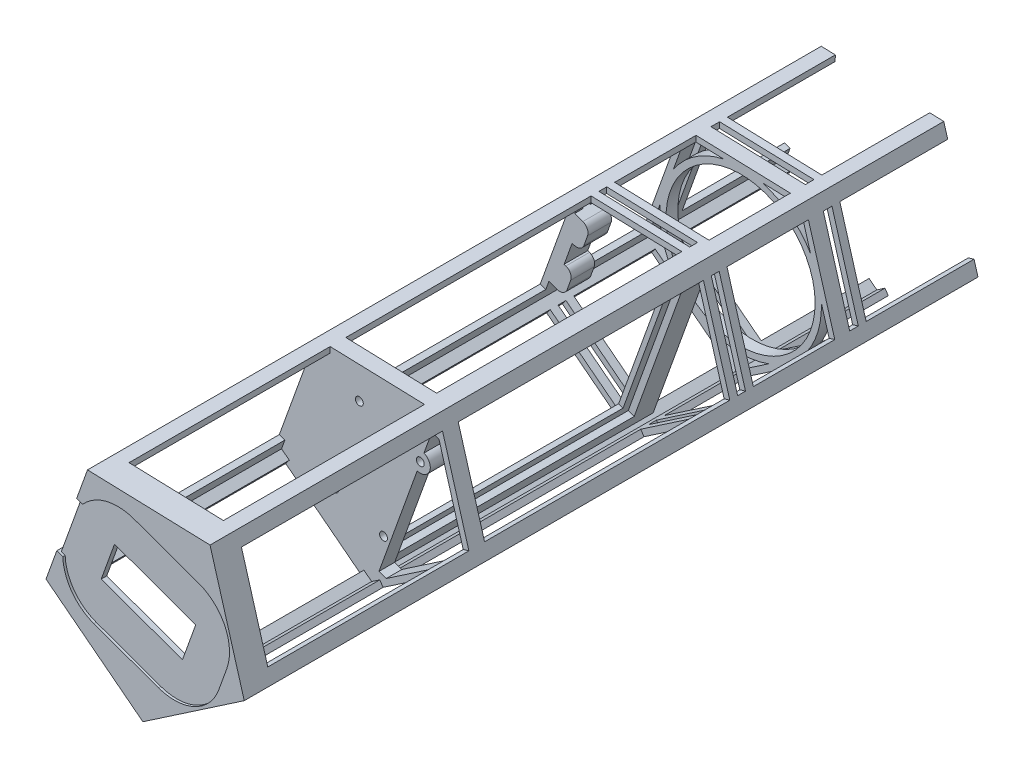
SolidWorks part; units mm, degrees
ref_plane "Front Plane" through (0, 0, 0) normal (0, 0, 1) x (1, 0, 0)
ref_plane "Top Plane" through (0, 0, 0) normal (0, 1, 0) x (1, 0, 0)
ref_plane "Right Plane" through (0, 0, 0) normal (1, 0, 0) x (0, 0, -1)
sketch "Sketch3" plane through (0, 0, 0) normal (0, 0, 1) x (1, 0, 0)
  line L0 (0, 0) -> (16.2851, 21.0012) construction
  line L1 (15.1489, 19.536) -> (-13.8986, 20.4445)
  line L2 (-13.8986, 20.4445) -> (-23.7387, -6.9006)
  line L3 (-23.7387, -6.9006) -> (-0.7728, -24.7093)
  line L4 (-0.7728, -24.7093) -> (23.2611, -8.3705)
  line L5 (0, 0) -> (29.9163, 0) construction
  line L6 (0, 0) -> (25.0057, -8.9983) construction
  line L10 (-0.8307, -26.5625) -> (25.0057, -8.9983)
  line L11 (25.0057, -8.9983) -> (16.2851, 21.0012)
  line L12 (16.2851, 21.0012) -> (-14.941, 21.9778)
  line L13 (-14.941, 21.9778) -> (-25.5191, -7.4182)
  line L14 (-25.5191, -7.4182) -> (-0.8307, -26.5625)
  line L15 (23.2611, -8.3705) -> (15.1489, 19.536)
  circle A0 centre (0, 0) radius 20 construction
  point P4 (0, 0)
  point P14 (0, 0)
  dimension "D2" = 40
extrude "Boss-Extrude2" add sketch "Sketch3" along normal blind 185
ref_plane "Plane1" through (0, 0, 92.5) normal (0, 0, 1) x (1, 0, 0)
sketch "Sketch4" plane through (0, 0, 0) normal (0, 0, -1) x (-1, 0, 0)
  line L0 (14.745, 18.0921) -> (16.1564, 18.6)
  line L1 (13.8986, 20.4445) -> (23.7387, -6.9006) construction
  line L2 (14.941, 21.9778) -> (25.5191, -7.4182) construction
  line L3 (24.3036, -4.0404) -> (22.8922, -4.5483)
  line L4 (22.8922, -4.5483) -> (14.745, 18.0921)
  line L5 (24.3036, -4.0404) -> (16.1564, 18.6)
  dimension "D1" = 2.5
  dimension "D2" = 2.5
extrude "Cut-Extrude1" cut sketch "Sketch4" against normal offset from surface (180 mm away) 5 up to face at (0, 0, 185)
ref_point "Point1"
ref_axis "Axis1" through (0, 0, 185) along (0, 0, 1)
pattern_circular "CirPattern1" count 5 over 360 about axis through (0, 0, 185) along (0, 0, 1) of "Cut-Extrude1"
ref_plane "Plane2" through (0, 0, 92.5) normal (0, 0, 1) x (1, 0, 0)
sketch "Sketch5" plane through (0, 0, 92.5) normal (0, 0, 1) x (1, 0, 0)
  line L0 (-2.0696, -25.6018) -> (14.7182, 21.0502) construction
  line L2 (-24.1133, -8.5083) -> (-1.8275, -25.7895) construction
  line L3 (23.2611, -8.3705) -> (0, 0) construction
  line L4 (-4.3961, -23.7977) -> (11.7756, 21.1422)
  line L8 (-2.0696, -25.6018) -> (-4.3961, -23.7977)
  line L10 (14.7182, 21.0502) -> (11.7756, 21.1422)
  line L11 (-2.0696, -25.6018) -> (14.7182, 21.0502)
  line L12 (-22.8004, 22.2236) -> (6.2471, 21.3151) construction
  dimension "D1" = 18
  dimension "D2" = 2.8
extrude "Boss-Extrude3" add sketch "Sketch5" along normal mid plane 64.5
sketch "Sketch6" plane through (0, 0, 124.75) normal (0, 0, 1) x (1, 0, 0)
  line L5 (-25.5191, -7.4182) -> (-0.8307, -26.5625)
  line L6 (-0.8307, -26.5625) -> (25.0057, -8.9983)
  line L7 (25.0057, -8.9983) -> (16.2851, 21.0012)
  line L8 (16.2851, 21.0012) -> (-14.941, 21.9778)
  line L9 (-14.941, 21.9778) -> (-25.5191, -7.4182)
  line L10 (-25.5191, -7.4182) -> (-0.8307, -26.5625)
  line L11 (-0.8307, -26.5625) -> (25.0057, -8.9983)
  line L12 (25.0057, -8.9983) -> (16.2851, 21.0012)
  line L13 (16.2851, 21.0012) -> (-14.941, 21.9778)
  line L14 (-14.941, 21.9778) -> (-25.5191, -7.4182)
  dimension "D1" = 0
extrude "Boss-Extrude4" add sketch "Sketch6" along normal blind 4
sketch "Sketch7" plane through (0, 0, 124.75) normal (0, 0, -1) x (-1, 0, 0)
  line L0 (-3.6897, -1.3278) -> (20.23, 7.2798) construction
  line L1 (-11.7756, 21.1422) -> (4.3961, -23.7977) construction
  line L2 (16.1564, 18.6) -> (24.3036, -4.0404) construction
  line L4 (19.0326, -2.4504) -> (13.1071, 14.0159)
  line L5 (0.2139, -9.2223) -> (-5.7115, 7.244)
  line L7 (19.0326, -2.4504) -> (-5.7115, 7.244) construction
  line L8 (0.2139, -9.2223) -> (13.1071, 14.0159) construction
  line L9 (9.6232, -5.8364) -> (3.6978, 10.63) construction
  line L11 (-11.7756, 21.1422) -> (4.3961, -23.7977) construction
  arc A0 (-5.7115, 7.244) -> (13.1071, 14.0159) centre (3.6978, 10.63) cw
  arc A1 (0.2139, -9.2223) -> (19.0326, -2.4504) centre (9.6232, -5.8364) ccw
  point P7 (6.6605, 2.3968)
  point P9 (13.0092, -15.2457)
  point P14 (0.3119, 20.0393)
  point P15 (0, 0)
  point P16 (7.1485, 2.5724)
  point P17 (7.4662, 2.6867)
  dimension "D1" = 37.5
  dimension "D2" = 20
  dimension "D3" = 1
extrude "Cut-Extrude2" cut sketch "Sketch7" against normal blind 2
sketch "Sketch8" plane through (6.3243, -2.2758, 0) normal (0.9409, -0.3386, 0) x (0, 0, -1)
  line L0 (-60.25, 0) -> (-124.75, 0) construction
  line L1 (-124.75, -23.2131) -> (-124.75, 23.2131) construction
  line L3 (-60.25, -23.2131) -> (-60.25, 23.2131) construction
  line L5 (-123, -20.5) -> (-123, 20.5)
  line L6 (-123, -20.5) -> (-62, -20.5)
  line L7 (-123, 20.5) -> (-62, 20.5)
  line L8 (-62, -20.5) -> (-62, 20.5)
  line L14 (-62, 20.5) -> (-123, -20.5) construction
  line L15 (-62, -20.5) -> (-123, 20.5) construction
  point P2 (0, 0)
  point P5 (0, 0)
  point P6 (0, 0)
  point P11 (-92.5, 0)
  point P14 (-92.5, 0)
  dimension "D1" = 61
  dimension "D2" = 41
extrude "Cut-Extrude3" cut sketch "Sketch8" against normal blind 1.6
sketch "Sketch9" plane through (4.8189, -1.7341, 0) normal (0.9409, -0.3386, 0) x (0, 0, -1)
  line L8 (-121, -18.5) -> (-64, -18.5)
  line L9 (-64, -18.5) -> (-64, 18.5)
  line L10 (-64, 18.5) -> (-121, 18.5)
  line L11 (-121, 18.5) -> (-121, -18.5)
  line L12 (-121, -18.5) -> (-64, -18.5)
  line L13 (-64, -18.5) -> (-64, 18.5)
  line L14 (-64, 18.5) -> (-121, 18.5)
  line L15 (-121, 18.5) -> (-121, -18.5)
  dimension "D1" = 2
extrude "Cut-Extrude4" cut sketch "Sketch9" against normal up to surface (1.2 mm away) up to face at (3.6897, -1.3278, 92.5)
sketch "Sketch10" plane through (0, 0, 60.25) normal (0, 0, -1) x (-1, 0, 0)
  line L25 (-23.2611, -8.3705) -> (0.7728, -24.7093)
  line L26 (0.7728, -24.7093) -> (23.7387, -6.9006)
  line L27 (23.7387, -6.9006) -> (13.8986, 20.4445)
  line L28 (13.8986, 20.4445) -> (-15.1489, 19.536)
  line L29 (-15.1489, 19.536) -> (-23.2611, -8.3705)
  line L30 (0.8307, -26.5625) -> (25.5191, -7.4182)
  line L31 (-25.0057, -8.9983) -> (0.8307, -26.5625)
  line L32 (-16.2851, 21.0012) -> (-25.0057, -8.9983)
  line L33 (14.941, 21.9778) -> (-16.2851, 21.0012)
  line L34 (25.5191, -7.4182) -> (14.941, 21.9778)
  line L40 (0.8307, -26.5625) -> (25.5191, -7.4182)
  line L41 (-25.0057, -8.9983) -> (0.8307, -26.5625)
  line L42 (-16.2851, 21.0012) -> (-25.0057, -8.9983)
  line L43 (14.941, 21.9778) -> (-16.2851, 21.0012)
  line L44 (25.5191, -7.4182) -> (14.941, 21.9778)
  point P8 (0, 0)
  point P11 (-0.8687, -22.1155)
  dimension "D1" = 0
extrude "Boss-Extrude5" add sketch "Sketch10" against normal blind 2
sketch "Sketch11" plane through (0, 0, 60.25) normal (0, 0, -1) x (-1, 0, 0)
  line L0 (3.8621, -22.3137) -> (4.3961, -23.7977)
  line L1 (4.3961, -23.7977) -> (3.6676, -24.3627)
  line L2 (-11.2416, 19.6582) -> (-11.7756, 21.1422)
  line L3 (-11.7756, 21.1422) -> (-12.697, 21.1134)
  line L4 (21.7631, -8.4326) -> (3.8621, -22.3137)
  line L7 (3.8621, -22.3137) -> (-11.2416, 19.6582)
  line L9 (-14.1842, 19.5662) -> (1.5355, -24.1178)
  line L10 (-14.1842, 19.5662) -> (1.5355, -24.1178)
  line L11 (-12.697, 21.1134) -> (11.3529, 21.8656) construction
  line L13 (3.8621, -22.3137) -> (-11.2416, 19.6582) construction
  line L18 (22.6823, -9.618) -> (3.6676, -24.3627) construction
  line L19 (3.8621, -22.3137) -> (-11.2416, 19.6582)
  line L27 (-11.2416, 19.6582) -> (11.3998, 20.3663)
  line L31 (1.5355, -24.1178) -> (2.7484, -23.1773)
  line L33 (1.5355, -24.1178) -> (2.7484, -23.1773)
  line L35 (2.7484, -23.1773) -> (3.6676, -24.3627)
  line L37 (2.7484, -23.1773) -> (3.6676, -24.3627)
  line L39 (3.6676, -24.3627) -> (22.6823, -9.618)
  line L41 (22.6823, -9.618) -> (21.7631, -8.4326)
  line L43 (11.3998, 20.3663) -> (11.3529, 21.8656)
  line L45 (11.3529, 21.8656) -> (-12.697, 21.1134)
  line L47 (-12.697, 21.1134) -> (-12.6502, 19.6141)
  line L48 (-12.697, 21.1134) -> (-12.6502, 19.6141)
  line L49 (-12.6502, 19.6141) -> (-14.1842, 19.5662)
  line L50 (-12.6502, 19.6141) -> (-14.1842, 19.5662)
  dimension "D1" = 0
extrude "Boss-Extrude6" add sketch "Sketch11" along normal blind 4
sketch "Sketch12" plane through (0, 0, 56.25) normal (0, 0, -1) x (-1, 0, 0)
  line L0 (0.7728, -24.7093) -> (23.7387, -6.9006)
  line L1 (23.7387, -6.9006) -> (13.8986, 20.4445)
  line L2 (13.8986, 20.4445) -> (-15.1489, 19.536)
  line L3 (-15.1489, 19.536) -> (-23.2611, -8.3705)
  line L4 (-23.2611, -8.3705) -> (0.7728, -24.7093)
  line L5 (0.8307, -26.5625) -> (25.5191, -7.4182)
  line L6 (-25.0057, -8.9983) -> (0.8307, -26.5625)
  line L7 (-16.2851, 21.0012) -> (-25.0057, -8.9983)
  line L8 (14.941, 21.9778) -> (-16.2851, 21.0012)
  line L9 (25.5191, -7.4182) -> (14.941, 21.9778)
  line L10 (0.8307, -26.5625) -> (25.5191, -7.4182)
  line L11 (-25.0057, -8.9983) -> (0.8307, -26.5625)
  line L12 (-16.2851, 21.0012) -> (-25.0057, -8.9983)
  line L13 (14.941, 21.9778) -> (-16.2851, 21.0012)
  line L14 (25.5191, -7.4182) -> (14.941, 21.9778)
  point P15 (0, -21.7043)
  dimension "D1" = 0
extrude "Boss-Extrude7" add sketch "Sketch12" against normal blind 2
ref_plane "Plane3" through (0, 0, 32.5) normal (0, 0, 1) x (1, 0, 0)
sketch "Sketch14" plane through (0, 0, 32.5) normal (0, 0, 1) x (1, 0, 0)
  line L5 (-25.5191, -7.4182) -> (-0.8307, -26.5625)
  line L6 (-0.8307, -26.5625) -> (25.0057, -8.9983)
  line L7 (25.0057, -8.9983) -> (16.2851, 21.0012)
  line L8 (16.2851, 21.0012) -> (-14.941, 21.9778)
  line L9 (-14.941, 21.9778) -> (-25.5191, -7.4182)
  line L11 (-0.8307, -26.5625) -> (25.0057, -8.9983)
  line L12 (25.0057, -8.9983) -> (16.2851, 21.0012)
  line L16 (23.2611, -8.3705) -> (15.3259, -13.7651)
  line L18 (-0.7728, -24.7093) -> (-8.3554, -18.8294)
  line L20 (-23.7387, -6.9006) -> (-20.4898, 2.1279)
  line L22 (-13.8986, 20.4445) -> (-4.308, 20.1445)
  line L24 (15.1489, 19.536) -> (17.8273, 10.3221)
  line L25 (7.1625, -19.3147) -> (-0.7728, -24.7093)
  line L26 (20.5827, 0.8433) -> (23.2611, -8.3705)
  line L27 (5.5584, 19.8359) -> (15.1489, 19.536)
  line L28 (-17.1475, 11.416) -> (-13.8986, 20.4445)
  line L29 (-16.1561, -12.7805) -> (-23.7387, -6.9006)
  line L30 (16.2851, 21.0012) -> (-14.941, 21.9778)
  line L31 (-14.941, 21.9778) -> (-25.5191, -7.4182)
  line L32 (-25.5191, -7.4182) -> (-0.8307, -26.5625)
  circle A3 centre (0, 0) radius 19
  arc A8 (15.3259, -13.7651) -> (20.5827, 0.8433) centre (0, 0) ccw
  circle A9 centre (0, 0) radius 20.6 construction
  arc A10 (17.8273, 10.3221) -> (5.5584, 19.8359) centre (0, 0) ccw
  arc A11 (-4.308, 20.1445) -> (-17.1475, 11.416) centre (0, 0) ccw
  arc A12 (-20.4898, 2.1279) -> (-16.1561, -12.7805) centre (0, 0) ccw
  arc A13 (-8.3554, -18.8294) -> (7.1625, -19.3147) centre (0, 0) ccw
  dimension "D2" = 38
  dimension "D1" = 0
  dimension "D3" = 1.6
extrude "Boss-Extrude8" add sketch "Sketch14" along normal blind 3
ref_plane "Plane4" through (0, 0, 29.5) normal (0, 0, -1) x (-1, 0, 0)
sketch "Sketch15" plane through (0, 0, 29.5) normal (0, 0, -1) x (-1, 0, 0)
  line L0 (-23.2611, -8.3705) -> (0.7728, -24.7093)
  line L1 (0.7728, -24.7093) -> (23.7387, -6.9006)
  line L2 (23.7387, -6.9006) -> (13.8986, 20.4445)
  line L3 (13.8986, 20.4445) -> (-15.1489, 19.536)
  line L4 (-15.1489, 19.536) -> (-23.2611, -8.3705)
  line L5 (0.8307, -26.5625) -> (25.5191, -7.4182)
  line L6 (-25.0057, -8.9983) -> (0.8307, -26.5625)
  line L7 (-16.2851, 21.0012) -> (-25.0057, -8.9983)
  line L8 (14.941, 21.9778) -> (-16.2851, 21.0012)
  line L9 (25.5191, -7.4182) -> (14.941, 21.9778)
  line L10 (0.8307, -26.5625) -> (25.5191, -7.4182)
  line L11 (-25.0057, -8.9983) -> (0.8307, -26.5625)
  line L12 (-16.2851, 21.0012) -> (-25.0057, -8.9983)
  line L13 (14.941, 21.9778) -> (-16.2851, 21.0012)
  line L14 (25.5191, -7.4182) -> (14.941, 21.9778)
  point P15 (-13.7443, 17.3013)
  point P16 (-15.1489, 19.536)
  dimension "D1" = 0
extrude "Boss-Extrude9" add sketch "Sketch15" along normal blind 2
sketch "Sketch18" plane through (0, 0, 32.5) normal (0, 0, -1) x (-1, 0, 0)
  line L0 (22.8922, -4.5483) -> (24.3036, -4.0404)
  line L1 (24.3036, -4.0404) -> (16.1564, 18.6)
  line L2 (16.1564, 18.6) -> (14.745, 18.0921)
  line L3 (14.745, 18.0921) -> (22.8922, -4.5483)
  line L4 (11.3998, 20.3663) -> (11.3529, 21.8656)
  line L5 (11.3529, 21.8656) -> (-12.697, 21.1134)
  line L6 (-12.697, 21.1134) -> (-12.6502, 19.6141)
  line L7 (-12.6502, 19.6141) -> (11.3998, 20.3663)
  line L8 (-15.8468, 17.1354) -> (-17.2872, 17.5541)
  line L9 (-17.2872, 17.5541) -> (-24.0037, -5.5512)
  line L10 (-24.0037, -5.5512) -> (-22.5633, -5.9699)
  line L11 (-22.5633, -5.9699) -> (-15.8468, 17.1354)
  line L12 (-21.1936, -9.7761) -> (-22.0369, -11.0166)
  line L13 (-22.0369, -11.0166) -> (-2.138, -24.5443)
  line L14 (-2.138, -24.5443) -> (-1.2947, -23.3038)
  line L15 (-1.2947, -23.3038) -> (-21.1936, -9.7761)
  line L16 (3.6676, -24.3627) -> (22.6823, -9.618)
  line L17 (22.6823, -9.618) -> (21.7631, -8.4326)
  line L18 (21.7631, -8.4326) -> (2.7484, -23.1773)
  line L19 (2.7484, -23.1773) -> (3.6676, -24.3627)
extrude "Boss-Extrude10" add sketch "Sketch18" along normal blind 0.8
sketch "Sketch25" plane through (0, 0, 56.25) normal (0, 0, -1) x (-1, 0, 0)
  line L0 (23.5979, -4.2944) -> (15.4507, 18.3461) construction
  line L1 (15.0407, 12.1611) -> (19.3409, 0.2112) construction
  line L2 (16.24, 16.1529) -> (11.5729, 14.4735)
  line L3 (24.3036, -4.0404) -> (22.8922, -4.5483) construction
  line L8 (14.745, 18.0921) -> (16.1564, 18.6) construction
  line L9 (22.5345, -1.339) -> (16.5142, 15.3907) construction
  line L10 (22.5345, -1.339) -> (4.6097, -7.7893) construction
  line L11 (16.5142, 15.3907) -> (-1.4105, 8.9405) construction
  line L12 (4.6097, -7.7893) -> (-1.4105, 8.9405) construction
  line L13 (19.5243, 7.0259) -> (0, 0) construction
  line L14 (16.24, 16.1529) -> (18.5086, 9.8487) construction
  line L15 (11.5729, 14.4735) -> (13.8415, 8.1692)
  line L16 (16.175, 9.0089) -> (13.8415, 8.1692)
  line L17 (13.9065, 15.3132) -> (16.175, 9.0089) construction
  line L18 (17.3743, 13.0008) -> (12.7072, 11.3213) construction
  line L19 (21.6744, 1.0509) -> (17.0074, -0.6285) construction
  line L20 (20.4752, -2.9409) -> (18.2066, 3.3633) construction
  line L21 (18.2066, 3.3633) -> (15.8731, 2.5236)
  line L22 (18.1417, -3.7806) -> (15.8731, 2.5236)
  line L23 (22.8087, -2.1012) -> (20.5401, 4.2031) construction
  line L24 (22.8087, -2.1012) -> (18.1417, -3.7806)
  line L25 (18.5086, 9.8487) -> (20.5401, 4.2031) construction
  line L28 (16.175, 9.0089) -> (18.2066, 3.3633)
  line L29 (16.24, 16.1529) -> (16.9457, 16.4068)
  line L30 (24.3036, -4.0404) -> (16.1564, 18.6) construction
  line L31 (16.9457, 16.4068) -> (23.5144, -1.8472)
  line L32 (23.5144, -1.8472) -> (22.8087, -2.1012)
  circle A0 centre (15.0407, 12.1611) radius 1 construction
  circle A1 centre (19.3409, 0.2112) radius 1 construction
  circle A2 centre (19.3409, 0.2112) radius 1 construction
  point P17 (17.1908, 6.1861)
  dimension "D3" = 2
  dimension "D4" = 12.7
  dimension "D1" = 17.78
  dimension "D2" = 19.05
  dimension "D5" = 16.57
  dimension "D6" = 6
sketch "Sketch26" plane through (0, 0, 56.25) normal (0, 0, -1) x (-1, 0, 0)
  circle A0 centre (19.3409, 0.2112) radius 1 construction
  circle A1 centre (19.3409, 0.2112) radius 1
  circle A2 centre (15.0407, 12.1611) radius 1 construction
  circle A3 centre (15.0407, 12.1611) radius 1
sketch "Sketch28" plane through (0, 0, 56.25) normal (0, 0, -1) x (-1, 0, 0)
  line L0 (23.5979, -4.2944) -> (15.4507, 18.3461) construction
  line L1 (22.5345, -1.339) -> (4.6097, -7.7893) construction
  line L2 (4.6097, -7.7893) -> (-1.4105, 8.9405) construction
  line L3 (16.5142, 15.3907) -> (-1.4105, 8.9405) construction
  line L4 (22.5345, -1.339) -> (16.5142, 15.3907) construction
  line L5 (22.5345, -1.339) -> (4.6097, -7.7893) construction
  line L6 (4.6097, -7.7893) -> (-1.4105, 8.9405) construction
  line L7 (16.5142, 15.3907) -> (-1.4105, 8.9405) construction
  line L8 (22.7904, -1.4595) -> (16.6347, 15.6466)
  line L9 (16.6347, 15.6466) -> (-1.6664, 9.061)
  line L10 (4.4892, -8.0452) -> (-1.6664, 9.061)
  line L11 (22.7904, -1.4595) -> (4.4892, -8.0452)
  dimension "D1" = 0.2
extrude "Boss-Extrude12" add sketch "Sketch25" against normal up to surface (6 mm away) up to face at (-19.5243, 7.0259, 62.25)
extrude "Cut-Extrude6" cut sketch "Sketch26" against normal blind 5
fillet "Fillet1" radius 2 4 edges at (-18.1417, -3.7806, 59.25) (-15.8731, 2.5236, 59.25) (-13.8415, 8.1692, 59.25) (-11.5729, 14.4735, 59.25)
sketch "Sketch29" plane through (0, 0, 185) normal (0, 0, 1) x (1, 0, 0)
  line L5 (-25.5191, -7.4182) -> (-0.8307, -26.5625)
  line L6 (-0.8307, -26.5625) -> (25.0057, -8.9983)
  line L7 (25.0057, -8.9983) -> (16.2851, 21.0012)
  line L8 (16.2851, 21.0012) -> (-14.941, 21.9778)
  line L9 (-14.941, 21.9778) -> (-25.5191, -7.4182)
  line L10 (-25.5191, -7.4182) -> (-0.8307, -26.5625)
  line L11 (-0.8307, -26.5625) -> (25.0057, -8.9983)
  line L12 (25.0057, -8.9983) -> (16.2851, 21.0012)
  line L13 (16.2851, 21.0012) -> (-14.941, 21.9778)
  line L14 (-14.941, 21.9778) -> (-25.5191, -7.4182)
  dimension "D1" = 0
extrude "Boss-Extrude13" add sketch "Sketch29" along normal blind 2
sketch "Sketch30" plane through (0, 0, 187) normal (0, 0, 1) x (1, 0, 0)
  line L0 (25.0057, -8.9983) -> (-20.23, 7.2798) construction
  line L1 (-14.941, 21.9778) -> (-25.5191, -7.4182) construction
  line L2 (3.1542, -17.0767) -> (-13.3121, -11.1513)
  line L3 (18.5086, -9.8487) -> (20.5401, -4.2031)
  line L4 (-20.5401, 4.2031) -> (-18.5086, 9.8487)
  line L5 (13.3121, 11.1513) -> (-3.1542, 17.0767)
  line L6 (14.4454, -21.1398) -> (-14.4454, 21.1398) construction
  line L7 (-24.6033, -7.0881) -> (24.6033, 7.0881) construction
  line L8 (19.5243, -7.0259) -> (-19.5243, 7.0259) construction
  arc A0 (18.5086, -9.8487) -> (3.1542, -17.0767) centre (7.2174, -5.7855) cw
  arc A1 (-18.5086, 9.8487) -> (-3.1542, 17.0767) centre (-7.2174, 5.7855) cw
  arc A2 (-13.3121, -11.1513) -> (-20.5401, 4.2031) centre (-9.2489, 0.1399) cw
  arc A3 (20.5401, -4.2031) -> (13.3121, 11.1513) centre (9.2489, -0.1399) ccw
  point P4 (0, 0)
  point P5 (0, 0)
  point P26 (0, 0)
  dimension "D3" = 12
  dimension "D1" = 30
  dimension "D2" = 41.5
extrude "Cut-Extrude8" cut sketch "Sketch30" against normal blind 0.6
sketch "Sketch31" plane through (0, 0, 186.4) normal (0, 0, 1) x (1, 0, 0)
  line L0 (25.0057, -8.9983) -> (0, 0) construction
  line L1 (12.0432, 0.9801) -> (8.6573, -8.4292)
  line L2 (12.0432, 0.9801) -> (-8.6573, 8.4292)
  line L3 (8.6573, -8.4292) -> (-12.0432, -0.9801)
  line L4 (-8.6573, 8.4292) -> (-12.0432, -0.9801)
  line L5 (12.0432, 0.9801) -> (-12.0432, -0.9801) construction
  line L6 (8.6573, -8.4292) -> (-8.6573, 8.4292) construction
  line L7 (-10.3503, 3.7246) -> (10.3503, -3.7246) construction
  dimension "D1" = 22
  dimension "D2" = 10
extrude "Cut-Extrude9" cut sketch "Sketch31" against normal up to surface (1.4 mm away) up to face at (0, 0, 185)
sketch "Sketch32" plane through (0, 0, 187) normal (0, 0, 1) x (1, 0, 0)
  line L0 (0, 0) -> (-36.3954, 13.0969) construction
  line L1 (-22.7695, 0.2228) -> (-21.2398, -0.3276)
  line L3 (-14.941, 21.9778) -> (-25.5191, -7.4182) construction
  line L4 (-17.6906, 14.3368) -> (-16.1609, 13.7863)
  line L5 (-18.5086, 9.8487) -> (-20.5401, 4.2031) construction
  line L6 (-18.5086, 9.8487) -> (-20.5401, 4.2031)
  line L7 (-17.6906, 14.3368) -> (-22.7695, 0.2228)
  arc A0 (-20.5401, 4.2031) -> (-13.3121, -11.1513) centre (-9.2489, 0.1399) ccw construction
  arc A1 (-20.5401, 4.2031) -> (-13.3121, -11.1513) centre (-9.2489, 0.1399) ccw construction
  arc A3 (-3.1542, 17.0767) -> (-18.5086, 9.8487) centre (-7.2174, 5.7855) ccw construction
  arc A4 (-16.1609, 13.7863) -> (-18.5086, 9.8487) centre (-7.2174, 5.7855) ccw
  arc A5 (-20.5401, 4.2031) -> (-21.2398, -0.3276) centre (-9.2489, 0.1399) ccw
  point P5 (0, 0)
  dimension "D1" = 7.5
extrude "Cut-Extrude11" cut sketch "Sketch32" against normal up to surface (0.6 mm away) up to face at (0, 0, 186.4)
sketch "Sketch34" plane through (0, 0, 186.4) normal (0, 0, 1) x (1, 0, 0)
  line L0 (-22.7695, 0.2228) -> (-17.6906, 14.3368)
  line L1 (-22.7695, 0.2228) -> (-22.0638, -0.0311)
  line L2 (-17.6906, 14.3368) -> (-16.9849, 14.0828)
  line L3 (-22.0638, -0.0311) -> (-16.9849, 14.0828)
  line L4 (-13.3121, -11.1513) -> (3.1542, -17.0767)
  line L5 (18.5086, -9.8487) -> (20.5401, -4.2031)
  line L6 (13.3121, 11.1513) -> (-3.1542, 17.0767)
  line L7 (-18.5086, 9.8487) -> (-20.5401, 4.2031)
  line L8 (-13.3121, -11.1513) -> (3.1542, -17.0767) construction
  line L9 (18.5086, -9.8487) -> (20.5401, -4.2031) construction
  line L10 (13.3121, 11.1513) -> (-3.1542, 17.0767) construction
  line L11 (-18.5086, 9.8487) -> (-20.5401, 4.2031) construction
  arc A4 (3.1542, -17.0767) -> (18.5086, -9.8487) centre (7.2174, -5.7855) ccw
  arc A5 (20.5401, -4.2031) -> (13.3121, 11.1513) centre (9.2489, -0.1399) ccw
  arc A6 (-3.1542, 17.0767) -> (-18.5086, 9.8487) centre (-7.2174, 5.7855) ccw
  arc A7 (-20.5401, 4.2031) -> (-13.3121, -11.1513) centre (-9.2489, 0.1399) ccw
  arc A8 (3.1542, -17.0767) -> (18.5086, -9.8487) centre (7.2174, -5.7855) ccw construction
  arc A9 (20.5401, -4.2031) -> (13.3121, 11.1513) centre (9.2489, -0.1399) ccw construction
  arc A10 (-3.1542, 17.0767) -> (-18.5086, 9.8487) centre (-7.2174, 5.7855) ccw construction
  arc A11 (-20.5401, 4.2031) -> (-13.3121, -11.1513) centre (-9.2489, 0.1399) ccw construction
  dimension "D1" = 0
sketch "Sketch38" plane through (0, 0, 124.75) normal (0, 0, -1) x (-1, 0, 0)
  line L5 (13.8986, 20.4445) -> (-15.1489, 19.536)
  line L6 (-15.1489, 19.536) -> (-23.2611, -8.3705)
  line L7 (-23.2611, -8.3705) -> (0.7728, -24.7093)
  line L8 (0.7728, -24.7093) -> (23.7387, -6.9006)
  line L9 (23.7387, -6.9006) -> (13.8986, 20.4445)
  line L11 (-16.3988, 15.2363) -> (-23.2611, -8.3705)
  line L12 (-23.2611, -8.3705) -> (-2.9303, -22.1919)
  line L16 (-1.0956, -21.5316) -> (-2.9303, -22.1919)
  line L17 (0.03, -24.6596) -> (-15.6897, 19.0244)
  line L18 (-1.0956, -21.5316) -> (-14.5641, 15.8965)
  line L19 (-14.5641, 15.8965) -> (-16.3988, 15.2363)
  dimension "D3" = 1.6
  dimension "D4" = 1.6
  dimension "D1" = 0
  dimension "D2" = 1.6
extrude "Cut-Extrude14" cut sketch "Sketch38" against normal up to surface (4 mm away) up to face at (0, 0, 128.75)
sketch "Sketch40" plane through (-18.8186, 6.7719, 0) normal (0.9409, -0.3386, 0) x (0, 0, -1)
  line L0 (-185, 14.5309) -> (-185, -14.5309) construction
  line L1 (-185, 7.5) -> (-183.5, 7.5)
  line L2 (-185, 7.5) -> (-185, -7.5)
  line L3 (-185, -7.5) -> (-183.5, -7.5)
  line L4 (-183.5, 7.5) -> (-183.5, -7.5)
  line L5 (-183.5, 0) -> (-185, 0) construction
  point P8 (-185, -11.8004)
  point P9 (-185, 0)
  dimension "D1" = 15
  dimension "D2" = 1.5
extrude "Cut-Extrude15" cut sketch "Sketch40" against normal up to surface (1.5 mm away) up to face at (-23.909, -2.9438, 59.25)
sketch "Sketch41" plane through (-20.23, 7.2798, 0) normal (-0.9409, 0.3386, 0) x (0, 0, 1)
  line L0 (185, -7.5) -> (186.4, -7.5)
  line L1 (185, 7.5) -> (186.4, 7.5)
  line L2 (185, -7.5) -> (185, 7.5)
  line L3 (186.4, 7.5) -> (186.4, -7.5)
extrude "Cut-Extrude16" cut sketch "Sketch41" against normal blind 0.6
ref_plane "Plane5" through (14.5641, 15.8965, 124.75) normal (0.3386, 0.9409, 0) x (0.9409, -0.3386, 0)
sketch "Sketch42" plane through (0, 0, 128.75) normal (0, 0, 1) x (1, 0, 0)
  line L0 (-20.23, 7.2798) -> (0, 0) construction
  line L1 (-16.1564, 18.6) -> (-24.3036, -4.0404) construction
  line L2 (5.4365, -16.774) -> (-14.8782, -9.4637) construction
  line L3 (5.4365, -16.774) -> (14.8782, 9.4637) construction
  line L4 (-14.8782, -9.4637) -> (-5.4365, 16.774) construction
  line L5 (14.8782, 9.4637) -> (-5.4365, 16.774) construction
  line L6 (5.4365, -16.774) -> (-5.4365, 16.774) construction
  line L7 (-14.8782, -9.4637) -> (14.8782, 9.4637) construction
  line L8 (-3.9066, 13.524) -> (11.6282, 7.9338) construction
  line L9 (4.7208, 13.1189) -> (-4.7208, -13.1189) construction
  line L10 (2.2472, -13.2032) -> (-10.1449, -8.7439) construction
  line L11 (-1.5355, -24.1178) -> (14.1842, 19.5662) construction
  line L12 (-1.5355, -24.1178) -> (14.1842, 19.5662)
  line L13 (12.891, 3.9416) -> (6.1392, -14.8212) construction
  line L14 (12.891, 3.9416) -> (10.6328, 4.7542) construction
  line L15 (6.1392, -14.8212) -> (3.881, -14.0086) construction
  line L16 (10.6328, 4.7542) -> (3.881, -14.0086) construction
  circle A0 centre (11.6282, 7.9338) radius 1
  circle A1 centre (-3.9066, 13.524) radius 1
  circle A2 centre (2.2472, -13.2032) radius 1
  circle A3 centre (-10.1449, -8.7439) radius 1
  point P1 (3.8608, 10.7289)
  point P2 (0, 0)
  point P19 (-3.9488, -10.9735)
  point P22 (-0.365, 0)
  point P23 (0, 0)
  point P24 (0, 0)
  point P25 (0, 0)
  dimension "D4" = 2
  dimension "D7" = 2
  dimension "D1" = 21.59
  dimension "D2" = 27.8848
  dimension "D3" = 16.51
  dimension "D5" = 2.54
  dimension "D6" = 13.17
  dimension "D8" = 2.28
  dimension "D9" = 2.4
sketch "Sketch43" plane through (0, 0, 128.75) normal (0, 0, 1) x (1, 0, 0)
  line L1 (10.8306, 5.5214) -> (12.5507, 10.3013)
  line L2 (12.891, 3.9416) -> (10.6328, 4.7542) construction
  line L3 (12.891, 3.9416) -> (10.6328, 4.7542)
  line L4 (1.0956, -21.5316) -> (14.5641, 15.8965) construction
  arc A0 (12.5507, 10.3013) -> (10.8306, 5.5214) centre (11.6282, 7.9338) cw
  point P4 (12.5507, 10.3013)
  line M27 (1.0956, -21.5316) -> (14.5641, 15.8965)
  dimension "D1" = 2.5409
extrude "Boss-Extrude15" add sketch "Sketch43" against normal up to surface (4 mm away) contours A0 M27 region at (12.6767, 7.5565, 128.75) up to face at (11.7736, -4.2367, 124.75)
sketch "Sketch44" plane through (0, 0, 128.75) normal (0, 0, 1) x (1, 0, 0)
  circle A0 centre (-10.1449, -8.7439) radius 1 construction
  circle A1 centre (-3.9066, 13.524) radius 1 construction
  circle A2 centre (-10.1449, -8.7439) radius 1
  circle A3 centre (-3.9066, 13.524) radius 1
extrude "Cut-Extrude18" cut sketch "Sketch42" against normal blind 3.5 contours A0 | A2
extrude "Cut-Extrude19" cut sketch "Sketch44" against normal blind 1.5
